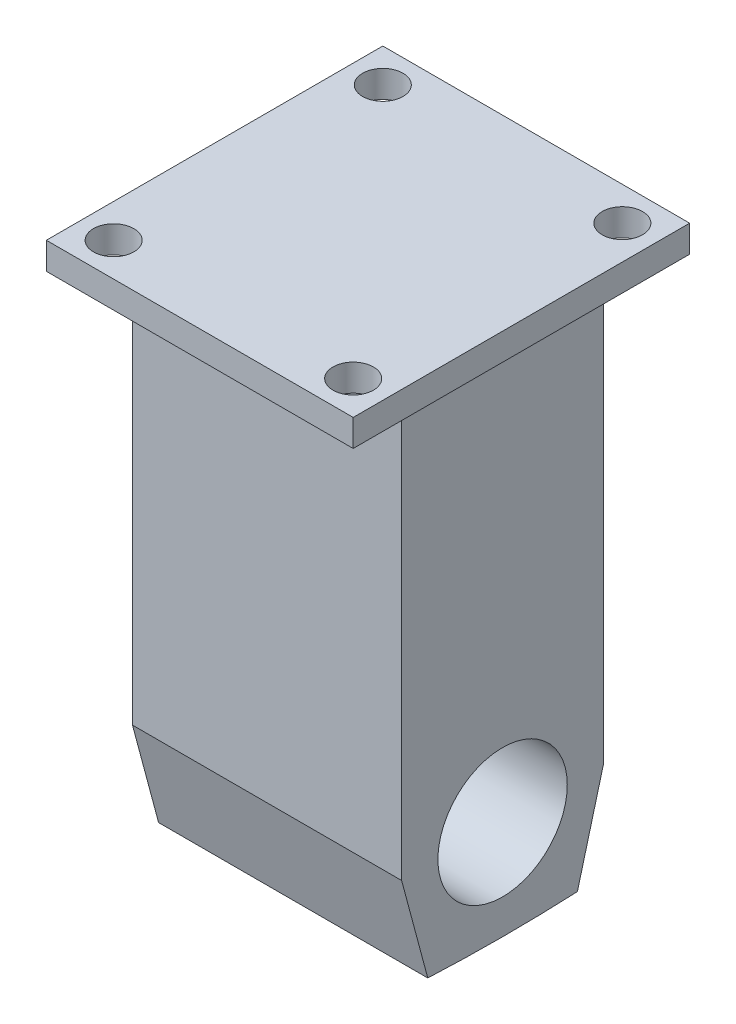
SolidWorks part; units mm, degrees
material "ABS"
ref_plane "Front Plane" through (0, 0, 0) normal (0, 0, 1) x (1, 0, 0)
ref_plane "Top Plane" through (0, 0, 0) normal (0, 1, 0) x (1, 0, 0)
ref_plane "Right Plane" through (0, 0, 0) normal (1, 0, 0) x (0, 0, -1)
sketch "Sketch1" plane through (0, 0, 0) normal (0, 1, 0) x (1, 0, 0)
  line L1 (-25.4, -19.05) -> (25.4, -19.05)
  line L2 (-25.4, -19.05) -> (-25.4, 19.05)
  line L3 (-25.4, 19.05) -> (25.4, 19.05)
  line L4 (25.4, -19.05) -> (25.4, 19.05)
  line L5 (-25.4, -19.05) -> (25.4, 19.05) construction
  line L6 (-25.4, 19.05) -> (25.4, -19.05) construction
  point P0 (0, 0)
extrude "Boss-Extrude1" add sketch "Sketch1" along normal blind 78.74
sketch "Sketch2" plane through (25.4, 0, 0) normal (1, 0, 0) x (0, 0, -1)
  line L0 (-19.05, 0) -> (-14.1195, -18.4009)
  line L1 (19.05, 0) -> (14.1195, -18.4009)
  line L2 (-19.05, 0) -> (19.05, 0)
  line L3 (-19.05, 0) -> (19.05, 0) construction
  arc A1 (14.1195, -18.4009) -> (-14.1195, -18.4009) centre (0, 281.2546) cw
  dimension "D1" = 19.05
  dimension "D2" = 19.05
  dimension "D3" = 75
  dimension "D4" = 75
extrude "Boss-Extrude2" add sketch "Sketch2" against normal up to vertex (50.8 mm away) contours L0 A1 L1 L2 up to point (-25.4, 0, -19.05)
sketch "Sketch3" plane through (25.4, 0, 0) normal (1, 0, 0) x (0, 0, -1)
  circle A0 centre (0, 0) radius 12.2085
extrude "Cut-Extrude1" cut sketch "Sketch3" against normal blind 127 contours A0
sketch "Sketch4" plane through (0, 78.74, 0) normal (0, 1, 0) x (1, 0, 0)
  line L1 (28.956, -31.75) -> (-28.956, -31.75)
  line L2 (28.956, -31.75) -> (28.956, 31.75)
  line L3 (28.956, 31.75) -> (-28.956, 31.75)
  line L4 (-28.956, -31.75) -> (-28.956, 31.75)
  line L5 (28.956, -31.75) -> (-28.956, 31.75) construction
  line L6 (28.956, 31.75) -> (-28.956, -31.75) construction
  point P0 (0, 0)
extrude "Boss-Extrude3" add sketch "Sketch4" along normal blind 5.08
sketch "Sketch5" plane through (0, 83.82, 0) normal (0, 1, 0) x (1, 0, 0)
  line L0 (0, -31.75) -> (0, 31.75) construction
  line L1 (28.956, 31.75) -> (-28.956, 31.75) construction
  line L2 (-28.956, 0) -> (28.956, 0) construction
  line L3 (28.956, -31.75) -> (28.956, 31.75) construction
  line L4 (-22.606, -31.75) -> (-22.606, 31.75) construction
  line L5 (-28.956, 25.4) -> (28.956, 25.4) construction
  line L6 (-28.956, 31.75) -> (-28.956, -31.75) construction
  circle A0 centre (-22.606, 25.4) radius 3.81
  circle A1 centre (-22.606, -25.4) radius 3.81
  circle A2 centre (22.606, 25.4) radius 3.81
  circle A3 centre (22.606, -25.4) radius 3.81
  point P6 (0, 0)
  point P12 (0, 0)
  point P15 (-22.606, 0)
  point P18 (0, 25.4)
  point P20 (-22.606, 25.4)
  dimension "D1" = 6.35
  dimension "D2" = 6.35
  dimension "D3" = 0
extrude "Cut-Extrude2" cut sketch "Sketch5" against normal blind 5.08
